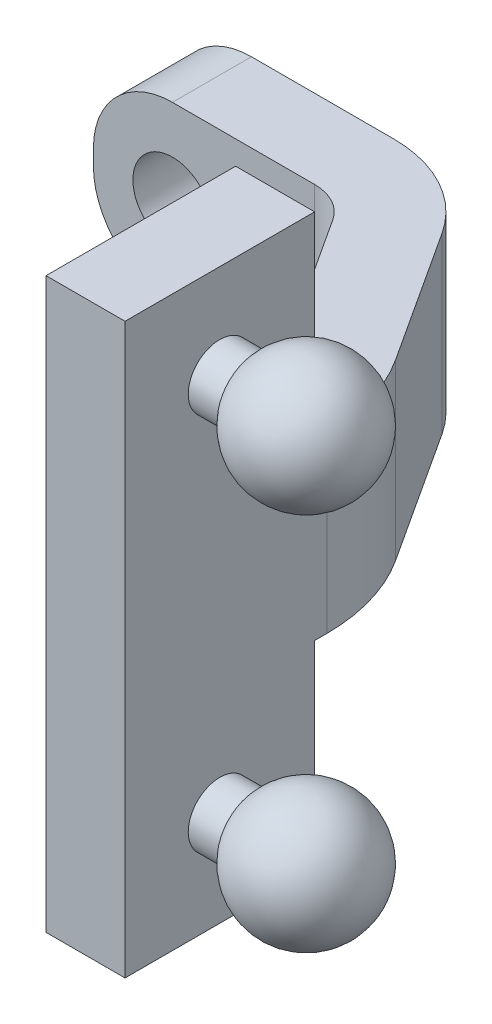
SolidWorks part; units mm, degrees
ref_plane "前视基准面" through (0, 0, 0) normal (0, 0, 1) x (1, 0, 0)
ref_plane "上视基准面" through (0, 0, 0) normal (0, 1, 0) x (1, 0, 0)
ref_plane "右视基准面" through (0, 0, 0) normal (1, 0, 0) x (0, 0, -1)
other "Configuration Table"
sketch "草图1" plane through (0, 0, 0) normal (0, 1, 0) x (1, 0, 0)
  line L0 (0, 0) -> (7, 0)
  line L1 (14, -9.1042) -> (14, -15.5)
  line L2 (0, -2.5) -> (7, -2.5)
  line L3 (11.5, -9.1042) -> (11.5, -15.5)
  line L4 (11.5, -15.5) -> (14, -15.5)
  line L5 (0, 0) -> (0, -2.5)
  line L6 (10.3535, -1.8196) -> (13.0862, -6.0224)
  line L7 (8.2575, -3.1823) -> (10.9903, -7.3852)
  arc A0 (7, 0) -> (10.3535, -1.8196) centre (7, -4) cw
  arc A3 (7, -2.5) -> (8.2575, -3.1823) centre (7, -4) cw
  arc A6 (9.6623, -0.4928) -> (14, -9.1042) centre (3.2834, -9.1042) cw construction
  arc A7 (10.3535, -1.8196) -> (9.6623, -0.4928) centre (16.8788, 2.4233) ccw construction
  arc A8 (8.2575, -3.1823) -> (7.6722, -2.1578) centre (16.8788, 2.4233) ccw construction
  arc A9 (7.6722, -2.1578) -> (11.5, -9.1042) centre (3.2834, -9.1042) cw construction
  arc A10 (13.0862, -6.0224) -> (14, -9.1042) centre (8.3466, -9.1042) cw
  arc A11 (11.5, -9.1042) -> (10.9903, -7.3852) centre (8.3466, -9.1042) ccw
  dimension "D1" = 2.5
  dimension "D3" = 4
  dimension "D4" = 14
  dimension "D2" = 7
  dimension "D6" = 15.5
extrude "凸台-拉伸1" add sketch "草图1" along normal mid plane 5.5
sketch "草图2" plane through (0, 0, 0) normal (0, 0, -1) x (-1, 0, 0)
  line L0 (0, 2.75) -> (0, -2.75) construction
  circle A0 centre (-2.5, 0) radius 1.25
  point P5 (0, 0)
  dimension "D1" = 2.5
  dimension "D2" = 2.5
extrude "切除-拉伸1" cut sketch "草图2" against normal blind 10
fillet "圆角2" radius 2.5 2 edges at (0, -2.75, 1.25) (0, 2.75, 1.25)
sketch "草图4" plane through (11.5, 0, 0) normal (-1, 0, 0) x (0, 0, 1)
  line L0 (15.5, 2.75) -> (15.5, -2.75) construction
  line L1 (9.5, 9) -> (15.5, 9)
  line L2 (9.5, 9) -> (9.5, -9)
  line L3 (9.5, -9) -> (15.5, -9)
  line L4 (15.5, 9) -> (15.5, -9)
  line L5 (9.5, 9) -> (15.5, -9) construction
  line L6 (9.5, -9) -> (15.5, 9) construction
  point P0 (12.5, 0)
  dimension "D1" = 18
  dimension "D2" = 6
extrude "凸台-拉伸2" add sketch "草图4" against normal up to surface (2.5 mm away) up to face at (14, 0, 12.3021)
sketch "草图5" plane through (14, 0, 0) normal (1, 0, 0) x (0, 0, -1)
  line L0 (-9.5, 9) -> (-15.5, 9) construction
  line L1 (-9.5, 2.75) -> (-9.5, 9) construction
  circle A0 centre (-12.5, 6) radius 1
  dimension "D1" = 2
  dimension "D2" = 3
  dimension "D3" = 3
extrude "凸台-拉伸3" add sketch "草图5" along normal blind 1
ref_axis "基准轴1" through (15, 6, 12.5) along (-1, 0, 0)
ref_plane "基准面1" through (0, 0, 12.5) normal (0, 0, -1) x (-1, 0, 0)
sketch "草图6" plane through (0, 0, 12.5) normal (0, 0, -1) x (-1, 0, 0)
  line L0 (-15, 6) -> (-18.7321, 6)
  line L1 (-15, 7) -> (-15, 5) construction
  line L2 (-15, 6) -> (-14, 6) construction
  line L3 (-15, 6) -> (-15, 7)
  line L4 (-14, 7) -> (-15, 7) construction
  arc A0 (-15, 7) -> (-18.7321, 6) centre (-16.7321, 6) ccw
  dimension "D1" = 4
revolve "旋转1" add sketch "草图6" angle 360 about L0
mirror "镜向1" about plane through (0, 0, 0) normal (0, 1, 0) of "凸台-拉伸3", "旋转1"
